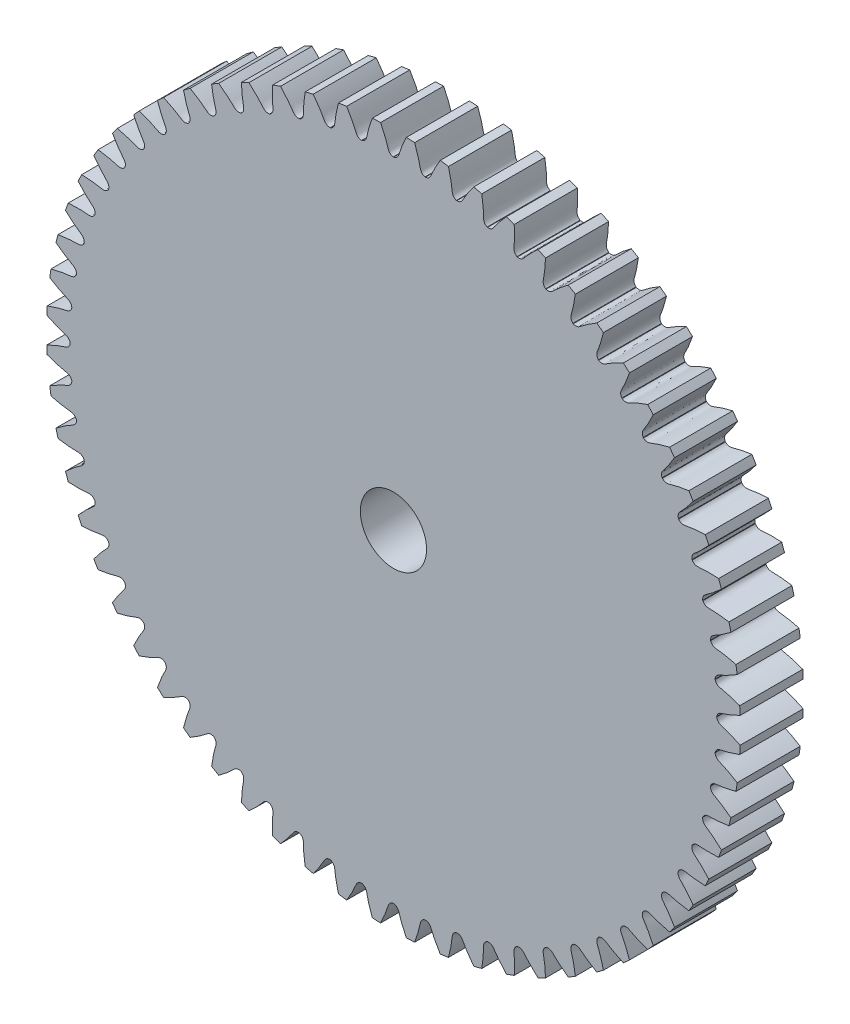
SolidWorks part; units mm, degrees
ref_plane "前视基准面" through (0, 0, 0) normal (0, 0, 1) x (1, 0, 0)
ref_plane "上视基准面" through (0, 0, 0) normal (0, 1, 0) x (1, 0, 0)
ref_plane "右视基准面" through (0, 0, 0) normal (1, 0, 0) x (0, 0, -1)
sketch "草图1" plane through (0, 0, 0) normal (0, 0, 1) x (1, 0, 0)
  circle A0 centre (0, 0) radius 16.5
extrude "凸台-拉伸1" add sketch "草图1" along normal blind 3
ref_axis "基准轴1" through (0, 0, -0.15) along (0, 0, 1)
sketch "草图2" plane through (0, 0, 0) normal (0, 0, 1) x (1, 0, 0)
  line L0 (0, 0) -> (0, 16.5) construction
  circle A0 centre (0, 0) radius 16.5 construction
  arc A1 (0.01, 15.3749) -> (-0.01, 15.3749) centre (0, 0) ccw
  arc A2 (2.2699, 18.763) -> (-2.2699, 18.763) centre (0, 0) ccw
  spline S0 degree 3 poles (0.01, 15.3749) (0.215, 15.4161) (0.2503, 15.5936) (0.3178, 15.7926) (0.3511, 15.8867) (0.3886, 15.9856) (0.4302, 16.0893) (0.4762, 16.1977) (0.5269, 16.3107) (0.5824, 16.4281) (0.6429, 16.5497) (0.7085, 16.6754) (0.7796, 16.805) (0.8563, 16.9385) (0.9387, 17.0755) (1.027, 17.2159) (1.1215, 17.3596) (1.2222, 17.5063) (1.3293, 17.6558) (1.4429, 17.808) (1.5633, 17.9626) (1.6906, 18.1195) (1.8248, 18.2784) (2.0159, 18.4957) (2.1662, 18.6564) (2.2699, 18.763) knots 0 0 0 0 0.106355 0.129132 0.153371 0.179072 0.206233 0.234857 0.264942 0.296488 0.329496 0.363966 0.399897 0.437289 0.476143 0.516459 0.558236 0.601475 0.646175 0.692337 0.73996 0.789045 0.839592 0.891599 1 1 1 1
  spline S1 degree 3 poles (-0.01, 15.3749) (-0.215, 15.4161) (-0.2503, 15.5936) (-0.3178, 15.7926) (-0.3511, 15.8867) (-0.3886, 15.9856) (-0.4302, 16.0893) (-0.4762, 16.1977) (-0.5269, 16.3107) (-0.5824, 16.4281) (-0.6429, 16.5497) (-0.7085, 16.6754) (-0.7796, 16.805) (-0.8563, 16.9385) (-0.9387, 17.0755) (-1.027, 17.2159) (-1.1215, 17.3596) (-1.2222, 17.5063) (-1.3293, 17.6558) (-1.4429, 17.808) (-1.5633, 17.9626) (-1.6906, 18.1195) (-1.8248, 18.2784) (-2.0159, 18.4957) (-2.1662, 18.6564) (-2.2699, 18.763) knots 0 0 0 0 0.106355 0.129132 0.153371 0.179072 0.206233 0.234857 0.264942 0.296488 0.329496 0.363966 0.399897 0.437289 0.476143 0.516459 0.558236 0.601475 0.646175 0.692337 0.73996 0.789045 0.839592 0.891599 1 1 1 1
extrude "切除-拉伸1" cut sketch "草图2" along normal through all
pattern_circular "阵列(圆周)1" count 64 every 5.625 about axis through (0, 0, -0.15) along (0, 0, 1) of "切除-拉伸1"
sketch "草图3" plane through (0, 0, 0) normal (0, 0, 1) x (1, 0, 0)
  circle A0 centre (0, 0) radius 16 construction
  dimension "Dn" = 32
sketch "草图4" plane through (0, 0, 0) normal (0, 0, -1) x (-1, 0, 0)
  circle A0 centre (0, 0) radius 5
  dimension "D1" = 10
extrude "凸台-拉伸2" add sketch "草图4" along normal blind 5
sketch "草图5" plane through (0, 0, -5) normal (0, 0, -1) x (-1, 0, 0)
  circle A0 centre (0, 0) radius 1.575
  dimension "D1" = 3.15
extrude "切除-拉伸2" cut sketch "草图5" against normal through all both
sketch "草图6" plane through (0, 0, 0) normal (0, 1, 0) x (1, 0, 0)
  line L0 (0, 5) -> (0, 2.5) construction
  line L1 (1.575, 5) -> (-1.575, 5) construction
  circle A0 centre (0, 2.5) radius 1
  dimension "D2" = 2
  dimension "D1" = 2.5
extrude "切除-拉伸3" cut sketch "草图6" against normal through all both and the other way through all
fillet "圆角1" radius 1 1 edges at (5, 0, 0)
